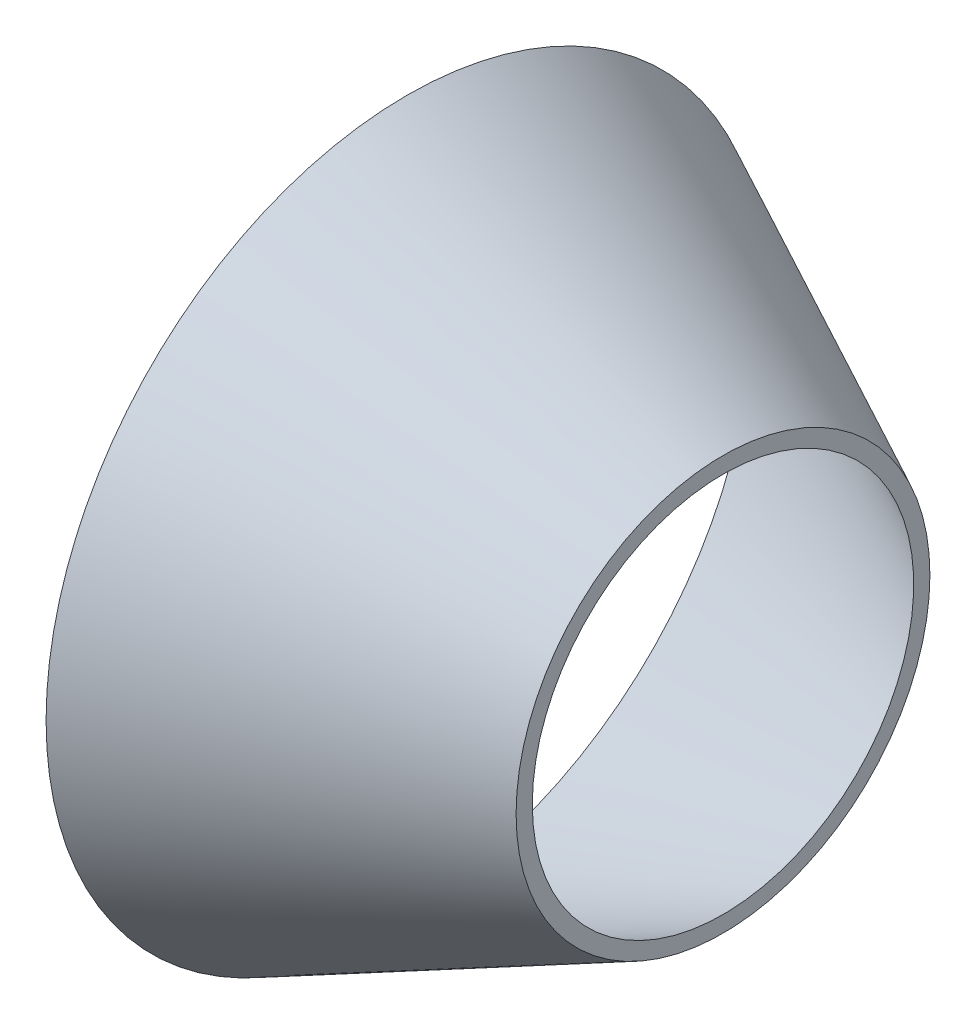
SolidWorks part; units mm, degrees
ref_plane "Front Plane" through (0, 0, 0) normal (0, 0, 1) x (1, 0, 0)
ref_plane "Top Plane" through (0, 0, 0) normal (0, 1, 0) x (1, 0, 0)
ref_plane "Right Plane" through (0, 0, 0) normal (1, 0, 0) x (0, 0, -1)
sketch "Sketch1" plane through (0, 0, 0) normal (0, 0, 1) x (1, 0, 0)
  line L0 (-564.6043, 0) -> (0, 0) construction
  line L1 (-130.7323, 261.9297) -> (-130.7323, 284.1817)
  line L2 (-130.7323, 261.9297) -> (-564.6043, 473.5432)
  line L4 (-46.2182, 242.9614) -> (-441.6876, 435.8447) construction
  line L5 (-564.6043, 495.7952) -> (-564.6043, 473.5432)
  line L10 (-54.9856, 224.9856) -> (-450.455, 417.8689) construction
  line L11 (-130.7323, 284.1817) -> (-564.6043, 495.7952)
  point P3 (-82, -57.4126)
  point P7 (-131.2866, 262.2)
  dimension "D1" = 284.1817
  dimension "D2" = 495.7952
  dimension "D3" = 433.8721
  dimension "D7" = 20
ref_plane "Plane3" through (0, 180, 0) normal (0, 1, 0) x (1, 0, 0)
revolve "Revolve2" add sketch "Sketch1" angle 360 about L0
sketch "Sketch2" plane through (0, 180, 0) normal (0, 1, 0) x (1, 0, 0)
  line L0 (-564.6043, 0) -> (-130.7323, 0) construction
  line L1 (-564.6043, 473.5432) -> (-564.6043, -473.5432) construction
  line L2 (-130.7323, -261.9297) -> (-130.7323, 261.9297) construction
  ellipse E1 centre (-195, 0) end of major axis (-195, -10) minor radius 6
  ellipse E2 centre (-315, 0) end of major axis (-315, -10) minor radius 6
  ellipse E3 centre (-455, 0) end of major axis (-455, -10) minor radius 6
  ellipse E5 centre (-555, 0) end of major axis (-555, -10) minor radius 6
  dimension "D3" = 120
  dimension "D4" = 140
  dimension "D5" = 100
extrude "Boss-Extrude2" add sketch "Sketch2" along normal up to surface and the other way blind 70 up to face at (-564.6043, 0, 495.7952)
sketch "Sketch3" plane through (0, 0, 0) normal (0, 0, 1) x (1, 0, 0)
  line L0 (-582.142, 0) -> (-582.142, 344.8882)
  line L1 (-582.142, 0) -> (62.9096, -0.5669)
  line L4 (-582.142, 344.8882) -> (62.9096, 172.0472)
  line L10 (62.9096, -0.5669) -> (62.9096, 172.0472)
  point P6 (-471.6828, 0)
  point P9 (-471.6828, 312.5748)
  dimension "D1" = 172.6141
sketch "Sketch4" plane through (0, 0, 0) normal (0, 1, 0) x (1, 0, 0)
  line L0 (-564.6043, 0) -> (-130.7323, 0) construction
  line L1 (-564.6043, 495.7952) -> (-564.6043, -495.7952) construction
  line L2 (-130.7323, -284.1817) -> (-130.7323, 284.1817) construction
revolve "Cut-Revolve1" cut sketch "Sketch3" angle 360 about L1 region at (-295.4053, 133.9027, 0)
